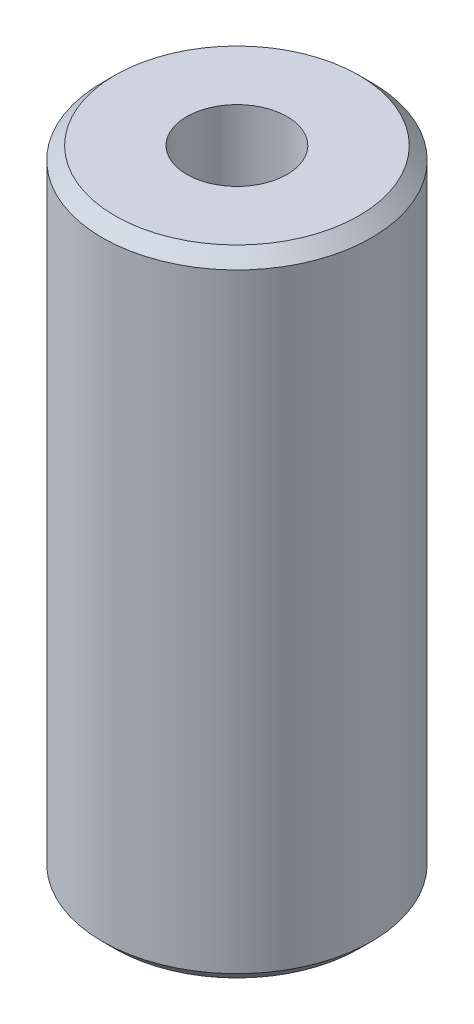
SolidWorks part; units mm, degrees
ref_plane "Front Plane" through (0, 0, 0) normal (0, 0, 1) x (1, 0, 0)
ref_plane "Top Plane" through (0, 0, 0) normal (0, 1, 0) x (1, 0, 0)
ref_plane "Right Plane" through (0, 0, 0) normal (1, 0, 0) x (0, 0, -1)
sketch "Sketch1" plane through (0, 0, 0) normal (0, 1, 0) x (1, 0, 0)
  circle A0 centre (0, 0) radius 52.5
  dimension "SHAFT_OD" = 105
extrude "Boss-Extrude1" add sketch "Sketch1" along normal blind 247.6971
sketch "Sketch2" plane through (0, 0, 0) normal (0, 1, 0) x (1, 0, 0)
  circle A0 centre (0, 0) radius 19.5683
  dimension "BORE_D" = 39.1366
extrude "Cut-Extrude1" cut sketch "Sketch2" along normal through all
chamfer "Chamfer1" distance 4.9454 angle 45 2 edges at (0, 247.6971, 52.5) (0, 0, 52.5)
